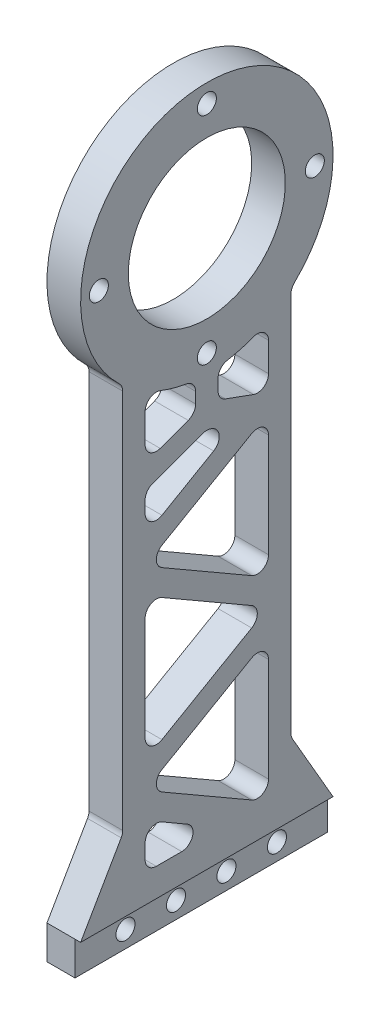
SolidWorks part; units mm, degrees
material "Сплав 2024"
ref_plane "Спереди" through (0, 0, 0) normal (0, 0, 1) x (1, 0, 0)
ref_plane "Сверху" through (0, 0, 0) normal (0, 1, 0) x (1, 0, 0)
ref_plane "Справа" through (0, 0, 0) normal (1, 0, 0) x (0, 0, -1)
sketch "Эскиз1" plane through (0, 0, 0) normal (0, 1, 0) x (1, 0, 0)
  line L1 (0, 0) -> (6, 0)
  line L2 (0, 0) -> (0, -30)
  line L3 (0, -30) -> (6, -30)
  line L4 (6, 0) -> (6, -30)
  dimension "D1" = 6
  dimension "D2" = 30
extrude "Бобышка-Вытянуть1" add sketch "Эскиз1" along normal blind 227
sketch "Эскиз2" plane through (0, 0, 0) normal (-1, 0, 0) x (0, 0, 1)
  line L0 (30, 105) -> (0, 105) construction
  line L3 (15, 227) -> (15, 0) construction
  line L4 (0, 227) -> (30, 227) construction
  line L5 (0, 0) -> (30, 0) construction
  line L6 (30, 0) -> (0, 0) construction
  circle A0 centre (15, 105) radius 22.5
  dimension "D1" = 45
  dimension "D2" = 105
extrude "Бобышка-Вытянуть2" add sketch "Эскиз2" against normal up to surface (6 mm away) up to face at (6, 113.5, 15)
sketch "Эскиз3" plane through (0, 0, 0) normal (-1, 0, 0) x (0, 0, 1)
  circle A0 centre (15, 105) radius 14
  dimension "D1" = 28
extrude "Вырез-Вытянуть1" cut sketch "Эскиз3" against normal through all
sketch "Эскиз4" plane through (6, 0, 0) normal (-1, 0, 0) x (0, 0, 1)
  line L0 (15, 127.5) -> (15, 82.5) construction
  line L1 (15, 227) -> (15, 0) construction
  line L2 (37.5, 105) -> (-7.5, 105) construction
  circle A0 centre (15, 105) radius 19.25 construction
  circle A1 centre (15, 105) radius 22.5 construction
  dimension "D1" = 38.5
hole_wizard "Отверстие с зазором M32" positions "Эскиз6" profile "Эскиз5" hole size "M3" standard "Ansi Metric" end condition through all
sketch "Эскиз6" plane through (6, -25.0247, 7.2629) normal (-1, 0, 0) x (0, 0, 1)
  line L0 (7.7371, 152.5247) -> (7.7371, 107.5247) construction
  line L1 (30.2371, 130.0247) -> (-14.7629, 130.0247) construction
  circle A0 centre (7.7371, 130.0247) radius 19.25 construction
  point P0 (7.7371, 149.2747)
  point P6 (-11.5129, 130.0247)
  point P10 (7.7371, 110.7747)
  point P12 (26.9871, 130.0247)
sketch "Эскиз5" plane through (6, 124.25, 15) normal (0, 1, 0) x (0, 0, -1)
  line L0 (0, 0) -> (0, 6)
  line L1 (0, 6) -> (1.7, 6)
  line L2 (1.7, 6) -> (1.7, 0)
  line L5 (1.7, 0) -> (0, 0)
  line L11 (0, -6.35) -> (0, 107.95) construction
  dimension "Диаметр сквозного отверстия" = 3.4
  dimension "Глубина сквозного отверстия" = 6
sketch "Эскиз8" plane through (6, 0, 0) normal (1, 0, 0) x (0, 0, -1)
  line L0 (-15, 227) -> (-15, 0) construction
  line L1 (-30, 227) -> (0, 227) construction
  line L2 (-30, 0) -> (0, 0) construction
  line L3 (19.447, 105) -> (-49.447, 105) construction
  line L4 (0, 227) -> (0, 121.7705) construction
  line L5 (-26, 145) -> (-4, 145) construction
  line L6 (-26, 145) -> (-26, 65) construction
  line L7 (-26, 65) -> (-4, 65) construction
  line L8 (-4, 145) -> (-4, 65) construction
  line L9 (-26, 145) -> (-4, 65) construction
  line L10 (-26, 65) -> (-4, 145) construction
  point P8 (-15, 105)
  point P9 (-15, 105)
  dimension "D1" = 4
  dimension "D2" = 80
  dimension "D3" = 105
sketch "Эскиз11" plane through (6, 0, 0) normal (1, 0, 0) x (0, 0, -1)
  line L0 (-30, 0) -> (0, 0) construction
  line L1 (-15, 227) -> (-15, 0) construction
  line L2 (-30, 227) -> (0, 227) construction
  line L3 (0, 88.2295) -> (0, 0) construction
  line L4 (-30, 88.2295) -> (-30, 0) construction
  line L5 (-37.5, 3) -> (7.5, 3) construction
  line L20 (-1.5, 0) -> (-1.5, 6) construction
  line L21 (-10.5, 0) -> (-10.5, 6) construction
  line L22 (-19.5, 0) -> (-19.5, 6) construction
  line L23 (-28.5, 0) -> (-28.5, 6) construction
  line L25 (-37.5, 0) -> (7.5, 6) construction
  line L26 (-37.5, 6) -> (7.5, 0) construction
  line L27 (-37.5, 6) -> (7.5, 6) construction
  line L28 (0, 18.9904) -> (7.5, 6)
  line L29 (-30, 18.9904) -> (0, 18.9904)
  line L30 (7.5, 6) -> (7.5, 0)
  line L31 (-37.5, 0) -> (7.5, 0)
  line L32 (-37.5, 6) -> (-37.5, 0)
  line L33 (-37.5, 6) -> (-30, 18.9904)
  point P2 (-15, 3)
  dimension "D1" = 45
  dimension "D2" = 6
  dimension "D3" = 9
  dimension "D4" = 9
  dimension "D5" = 9
  dimension "D6" = 9
  dimension "D7" = 120
extrude "Бобышка-Вытянуть3" add sketch "Эскиз11" against normal up to surface (6 mm away) up to face at (0, 124.25, 13.3)
hole_wizard "Отверстие с зазором M31" positions "Эскиз13" profile "Эскиз12" hole size "M3" standard "Ansi Metric" end condition through all
sketch "Эскиз13" plane through (6, 0, 0) normal (1, 0, 0) x (0, 0, -1)
  line L4 (-28.5, 0) -> (-28.5, 6) construction
  line L5 (-19.5, 0) -> (-19.5, 6) construction
  line L6 (-10.5, 0) -> (-10.5, 6) construction
  line L7 (-1.5, 0) -> (-1.5, 6) construction
  point P16 (-28.5, 3)
  point P20 (-19.5, 3)
  point P24 (-10.5, 3)
  point P28 (-1.5, 3)
sketch "Эскиз12" plane through (6, 3, 28.5) normal (0, 1, 0) x (0, 0, -1)
  line L0 (0, 0) -> (0, 6)
  line L1 (0, 6) -> (1.7, 6)
  line L2 (1.7, 6) -> (1.7, 0)
  line L5 (1.7, 0) -> (0, 0)
  line L11 (0, -6.35) -> (0, 107.95) construction
  dimension "Диаметр сквозного отверстия" = 3.4
  dimension "Глубина сквозного отверстия" = 6
sketch "Эскиз14" plane through (6, 0, 0) normal (1, 0, 0) x (0, 0, -1)
  line L5 (-37.5, 0) -> (7.5, 0)
  line L6 (-37.5, 0) -> (-37.5, 6)
  line L7 (-37.5, 6) -> (7.5, 6)
  line L8 (7.5, 0) -> (7.5, 6)
extrude "Вырез-Вытянуть2" cut sketch "Эскиз14" against normal blind 1
sketch "Эскиз15" plane through (6, 0, 0) normal (1, 0, 0) x (0, 0, -1)
  line L0 (0, 227) -> (0, 121.7705) construction
  line L1 (-30, 227) -> (0, 227)
  line L2 (-30, 227) -> (-30, 121.7705)
  line L4 (0, 227) -> (0, 121.7705)
  arc A1 (-30, 121.7705) -> (0, 121.7705) centre (-15, 105) cw
extrude "Вырез-Вытянуть3" cut sketch "Эскиз15" against normal up to surface (6 mm away) up to face at (0, 3, 26.8)
sketch "Эскиз16" [suppressed] plane through (6, 0, 0) normal (1, 0, 0) x (0, 0, -1)
  line L0 (-26, 0) -> (-26, 89.3005) construction
  line L1 (-37.5, 0) -> (7.5, 0) construction
  line L2 (-4, 0) -> (-4, 89.3005) construction
  line L3 (-30, 88.2295) -> (-30, 18.9904) construction
  line L4 (0, 88.2295) -> (0, 18.9904) construction
  line L5 (-30, 80.25) -> (0, 80.25) construction
  line L6 (-26, 80.25) -> (-4, 80.25)
  line L7 (-4, 80.25) -> (-26, 67.5483)
  line L8 (-26, 67.5483) -> (-26, 80.25)
  line L9 (-26, 62.9295) -> (-4, 75.6312)
  line L10 (-4, 75.6312) -> (-4, 50.2278)
  line L11 (-4, 50.2278) -> (-26, 62.9295)
  line L12 (-26, 58.3107) -> (-4, 45.609)
  line L13 (-4, 45.609) -> (-26, 32.9073)
  line L14 (-26, 32.9073) -> (-26, 58.3107)
  line L15 (-26, 28.2885) -> (-4, 40.9902)
  line L16 (-4, 40.9902) -> (-4, 15.5868)
  line L17 (-4, 15.5868) -> (-26, 28.2885)
  line L18 (-26, 23.6697) -> (-4, 10.968)
  line L19 (-4, 10.968) -> (-26, 10.968)
  line L20 (-26, 10.968) -> (-26, 23.6697)
  circle A2 centre (-15, 85.75) radius 1.7 construction
  dimension "D3" = 5.5
  dimension "D1" = 4
  dimension "D2" = 4
  dimension "D4" = 30
  dimension "D5" = 4
  dimension "D6" = 4
  dimension "D7" = 4
  dimension "D8" = 4
  dimension "D9" = 60
  dimension "D10" = 60
  dimension "D11" = 60
extrude "Вырез-Вытянуть4" [suppressed] cut sketch "Эскиз16" against normal through all
fillet "Скругление1" [suppressed] radius 2
chamfer "Фаска1" [suppressed] distance 1 angle 45
sketch "Эскиз17" plane through (6, 0, 0) normal (1, 0, 0) x (0, 0, -1)
  line L0 (-26, 0) -> (-26, 111.7401) construction
  line L1 (-37.5, 0) -> (7.5, 0) construction
  line L2 (-4, 0) -> (-4, 111.7401) construction
  line L3 (-30, 88.2295) -> (-30, 18.9904) construction
  line L4 (0, 88.2295) -> (0, 18.9904) construction
  line L5 (-17, 82.5891) -> (-17, 77.4791)
  line L6 (-13, 82.5891) -> (-13, 77.4791)
  line L7 (-15, 227) -> (-15, 0) construction
  line L8 (-17, 77.4791) -> (-26, 74.2033)
  line L9 (-30, 74.2033) -> (0, 74.2033) construction
  line L10 (-13, 77.4791) -> (-4, 74.2033)
  line L11 (-26, 85.3722) -> (-26, 74.2033)
  line L12 (-30, 77.4791) -> (0, 77.4791) construction
  line L13 (-4, 74.2033) -> (-4, 85.3722)
  line L14 (-26, 69.9466) -> (-15, 73.9503)
  line L15 (-15, 73.9503) -> (-10.073, 72.157)
  line L16 (-4, 71.0444) -> (-4, 45.641)
  line L17 (-26, 69.9466) -> (-26, 62.9615)
  line L18 (-26, 53.7239) -> (-4, 41.0222)
  line L19 (-4, 41.0222) -> (-26, 28.3205)
  line L20 (-26, 28.3205) -> (-26, 53.7239)
  line L21 (-26, 23.7017) -> (-4, 36.4034)
  line L22 (-4, 36.4034) -> (-4, 11)
  line L23 (-4, 11) -> (-26, 23.7017)
  line L24 (-26, 19.0829) -> (-12, 11)
  line L25 (-12, 11) -> (-26, 11)
  line L26 (-26, 11) -> (-26, 19.0829)
  line L27 (-34.6132, 11) -> (4.6132, 11) construction
  line L28 (-30, 18.9904) -> (-37.5, 6) construction
  line L29 (7.5, 6) -> (0, 18.9904) construction
  line L30 (7.5, 6) -> (-37.5, 6) construction
  line L31 (-26, 58.3427) -> (-4, 45.641)
  line L32 (-26, 58.3427) -> (-4, 71.0444) construction
  line L33 (-26, 62.9615) -> (-10.073, 72.157) construction
  line L35 (-26, 58.3427) -> (-4, 71.0444)
  line L36 (-10.073, 72.157) -> (-26, 62.9615)
  circle A0 centre (-15, 105) radius 22.5 construction
  arc A1 (-26, 85.3722) -> (-17, 82.5891) centre (-15, 105) ccw
  arc A2 (-13, 82.5891) -> (-4, 85.3722) centre (-15, 105) ccw
  point P10 (-26, 85.3722)
  point P11 (-4, 85.3722)
  dimension "D1" = 4
  dimension "D2" = 4
  dimension "D3" = 4
  dimension "D4" = 2
  dimension "D5" = 4
  dimension "D6" = 60
  dimension "D7" = 5.11
  dimension "D8" = 110
  dimension "D9" = 30
  dimension "D10" = 4
  dimension "D11" = 60
  dimension "D12" = 4
  dimension "D13" = 4
  dimension "D14" = 5
  dimension "D15" = 60
  dimension "D16" = 4
extrude "Вырез-Вытянуть5" cut sketch "Эскиз17" against normal up to next
fillet "Скругление2" radius 2 28 edges at (3, 74.2033, 4) (3, 77.4791, 13) (3, 74.2033, 26) (3, 82.5891, 13) (3, 85.3722, 4) (3, 82.5891, 17) (3, 85.3722, 26) (3, 62.9615, 26) (3, 69.9466, 26) (3, 72.157, 10.073) (3, 73.9503, 15) (3, 77.4791, 17) (3, 11, 26) (3, 19.0829, 26) (3, 11, 12) (3, 11, 4) (3, 36.4034, 4) (3, 23.7017, 26) (3, 28.3205, 26) (3, 53.7239, 26) (3, 41.0222, 4) (3, 45.641, 4) (3, 58.3427, 26) (3, 71.0444, 4) (3, 18.9904, 0) (3, 18.9904, 30) (3, 88.2295, 30) (3, 88.2295, 0)
equation "\"D4@Эскиз11\"=\"D3@Эскиз11\""
equation "\"D5@Эскиз11\"=\"D3@Эскиз11\""
equation "\"D6@Эскиз11\"=\"D4@Эскиз11\""
equation "\"D3@Эскиз11\" = \"D1@Эскиз11\" / 5"
equation "\"D10@Эскиз16\"=\"D4@Эскиз16\"*2"
equation "\"D9@Эскиз16\"=\"D10@Эскиз16\""
equation "\"D11@Эскиз16\"=\"D10@Эскиз16\""
